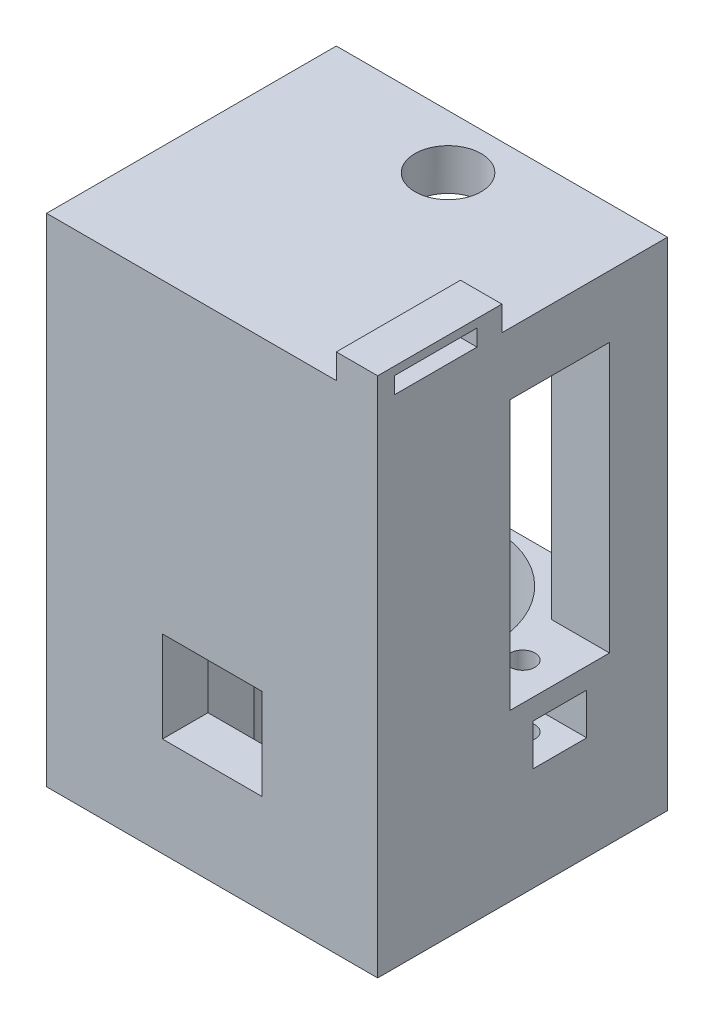
SolidWorks part; units mm, degrees
ref_plane "Plano frontal" through (0, 0, 0) normal (0, 0, 1) x (1, 0, 0)
ref_plane "Plano superior" through (0, 0, 0) normal (0, 1, 0) x (1, 0, 0)
ref_plane "Plano direito" through (0, 0, 0) normal (1, 0, 0) x (0, 0, -1)
sketch "Esboço2" plane through (0, 0, 0) normal (0, 1, 0) x (1, 0, 0)
  line L1 (0, 0) -> (40, 0)
  line L2 (0, 0) -> (0, 35)
  line L3 (0, 35) -> (40, 35)
  line L4 (40, 0) -> (40, 35)
  dimension "D1" = 40
  dimension "D2" = 35
extrude "Base" add sketch "Esboço2" along normal blind 20
sketch "Esboço3" plane through (0, 20, 0) normal (0, 1, 0) x (1, 0, 0)
  line L0 (20, -2.1425) -> (20, 46.202) construction
  line L1 (-2.8555, 22) -> (47.4642, 22) construction
  line L2 (40, 0) -> (40, 35) construction
  line L3 (40, 35) -> (0, 35) construction
  line L5 (11.25, 5.5) -> (28.75, 5.5)
  line L6 (11.25, 5.5) -> (11.25, 14.5)
  line L7 (11.25, 14.5) -> (28.75, 14.5)
  line L8 (28.75, 5.5) -> (28.75, 14.5)
  line L9 (11.25, 5.5) -> (28.75, 14.5) construction
  line L10 (11.25, 14.5) -> (28.75, 5.5) construction
  circle A0 centre (20, 22) radius 12
  point P10 (20, 10)
  dimension "D1" = 24
  dimension "D2" = 20
  dimension "D3" = 13
  dimension "D4" = 17.5
  dimension "D5" = 9
  dimension "D6" = 16.5
extrude "Furo do encaixe do motor" cut sketch "Esboço3" against normal through all contours A0 L7 L6 L5 L8 | L7 A0 | L7 A0 region at (20, 20, -8.4409) region at (20, 20, -23.3816) region at (20, 20, -12.6552)
sketch "Esboço5" plane through (0, 20, 0) normal (0, 1, 0) x (1, 0, 0)
  line L0 (41.6655, 22) -> (-3.8205, 22) construction
  line L1 (20, 37.517) -> (20, 6.483) construction
  circle A0 centre (4.5, 22) radius 1.5
  circle A1 centre (35.5, 22) radius 1.5
  point P10 (20, 22)
  dimension "D1" = 3
  dimension "D2" = 3
  dimension "D3" = 15.5
  dimension "D4" = 15.5
extrude "Furo dos parafusos do motor" cut sketch "Esboço5" against normal through all
sketch "Esboço6" plane through (40, 0, 0) normal (1, 0, 0) x (0, 0, -1)
  line L0 (22, 21.0896) -> (22, -1.5414) construction
  line L1 (35, 20) -> (35, 0) construction
  line L2 (0, 20) -> (35, 20) construction
  line L3 (18.75, 17.5) -> (25.25, 17.5)
  line L4 (18.75, 17.5) -> (18.75, 12.5)
  line L5 (18.75, 12.5) -> (25.25, 12.5)
  line L6 (25.25, 17.5) -> (25.25, 12.5)
  line L7 (18.75, 17.5) -> (25.25, 12.5) construction
  line L8 (18.75, 12.5) -> (25.25, 17.5) construction
  point P4 (22, 15)
  dimension "D1" = 13
  dimension "D2" = 6.5
  dimension "D3" = 5
  dimension "D4" = 5
extrude "Furo da arruela para parafusos do motor" cut sketch "Esboço6" against normal through all
sketch "Esboço7" plane through (0, 20, 0) normal (0, 1, 0) x (1, 0, 0)
  line L0 (20, 16.9507) -> (20, -1.8604) construction
  line L1 (40, 0) -> (40, 35) construction
  line L3 (14, -3.2615) -> (26, -3.2615)
  line L4 (14, -3.2615) -> (14, 18.3519)
  line L5 (14, 18.3519) -> (26, 18.3519)
  line L6 (26, -3.2615) -> (26, 18.3519)
  line L7 (14, -3.2615) -> (26, 18.3519) construction
  line L8 (14, 18.3519) -> (26, -3.2615) construction
  point P4 (20, 7.5452)
  dimension "D1" = 20
  dimension "D2" = 12
extrude "Calha para os cabos do motor" cut sketch "Esboço7" against normal blind 8
sketch "Esboço10" plane through (0, 20, 0) normal (0, 1, 0) x (1, 0, 0)
  line L0 (40, 0) -> (40, 35) construction
  line L1 (0, 35) -> (7, 35)
  line L2 (0, 35) -> (0, 28)
  line L3 (0, 28) -> (7, 28)
  line L4 (7, 35) -> (7, 28)
  line L5 (40, 35) -> (33, 35)
  line L6 (40, 35) -> (40, 28)
  line L7 (40, 28) -> (33, 28)
  line L8 (33, 35) -> (33, 28)
  line L9 (0, 0) -> (40, 0)
  line L10 (0, 0) -> (0, 5.5)
  line L11 (0, 5.5) -> (40, 5.5)
  line L12 (40, 0) -> (40, 5.5)
  line L14 (0, 5.5) -> (7, 5.5)
  line L15 (0, 5.5) -> (0, 16)
  line L16 (0, 16) -> (7, 16)
  line L17 (7, 5.5) -> (7, 16)
  line L18 (40, 5.5) -> (33, 5.5)
  line L19 (40, 5.5) -> (40, 16)
  line L20 (40, 16) -> (33, 16)
  line L21 (33, 5.5) -> (33, 16)
  line M13 (28.75, 5.5) -> (26, 5.5)
  line M14 (26, 5.5) -> (26, 0)
  line M15 (26, 0) -> (40, 0)
  line M16 (40, 0) -> (40, 35)
  line M17 (40, 35) -> (0, 35)
  line M18 (0, 35) -> (0, 0)
  line M19 (0, 0) -> (14, 0)
  line M20 (14, 0) -> (14, 5.5)
  line M21 (14, 5.5) -> (11.25, 5.5)
  dimension "D1" = 5.5
  dimension "D2" = 7
  dimension "D3" = 7
  dimension "D4" = 7
  dimension "D5" = 7
  dimension "D6" = 7
  dimension "D7" = 7
  dimension "D8" = 10.5
  dimension "D9" = 10.5
extrude "Base extendida" add sketch "Esboço10" along normal blind 35 contours L11 L17 L16 M18 | L11 M18 M19 M20 M21 | L11 M13 M14 M15 M16 | L11 L9 M20 M14 | L21 L11 L20 M16 | L8 L7 M17 M16 | L4 L3 M17 M18 region at (3.5, 20, -31.5) region at (36.5, 20, -31.5) region at (3.5, 20, -10.75) region at (7, 20, -2.75) region at (36.5, 20, -10.75) region at (20, 20, -2.75) region at (33, 20, -2.75)
sketch "Esboço11" plane through (7, 0, 0) normal (1, 0, 0) x (0, 0, -1)
  line L0 (16, 55) -> (16, 45)
  line L1 (16, 55) -> (16, 20) construction
  line L2 (16, 55) -> (5.5, 55)
  line L3 (5.5, 55) -> (16, 55) construction
  line L4 (5.5, 55) -> (5.5, 30.0044)
  line L5 (16, 45) -> (5.5, 30.0044)
  point P9 (10.75, 55)
  point P10 (5.5, 25.209)
  dimension "D1" = 10.5
  dimension "D2" = 35
  dimension "D3" = 10
extrude "Chanfro da base extendida" add sketch "Esboço11" along normal through all
sketch "Esboço12" plane through (0, 0, -16) normal (0, 0, -1) x (-1, 0, 0)
  line L1 (-40, 55) -> (-33, 55)
  line L2 (-40, 55) -> (-40, 52.5)
  line L3 (-40, 52.5) -> (-33, 52.5)
  line L4 (-33, 55) -> (-33, 52.5)
  dimension "D1" = 2.5
  dimension "D2" = 7
extrude "Ponte 1" add sketch "Esboço12" along normal through all
sketch "Esboço13" plane through (0, 0, -16) normal (0, 0, -1) x (-1, 0, 0)
  line L1 (0, 55) -> (-7, 55)
  line L2 (0, 55) -> (0, 52.5)
  line L3 (0, 52.5) -> (-7, 52.5)
  line L4 (-7, 55) -> (-7, 52.5)
  dimension "D1" = 2.5
  dimension "D2" = 7
extrude "Ponte 2" add sketch "Esboço13" along normal through all
sketch "Esboço14" plane through (0, 55, 0) normal (0, 1, 0) x (1, 0, 0)
  line L1 (0, 0) -> (40, 0)
  line L2 (0, 0) -> (0, 35)
  line L3 (0, 35) -> (40, 35)
  line L4 (40, 0) -> (40, 35)
extrude "Telhado" add sketch "Esboço14" along normal blind 5
sketch "Esboço16" plane through (0, 60, 0) normal (0, 1, 0) x (1, 0, 0)
  line L1 (40, 0) -> (35, 0)
  line L2 (40, 0) -> (40, 15)
  line L3 (40, 15) -> (35, 15)
  line L4 (35, 0) -> (35, 15)
  dimension "D1" = 5
  dimension "D2" = 15
extrude "Ressalto-extrusão6" add sketch "Esboço16" along normal blind 3
sketch "Esboço17" plane through (40, 0, 0) normal (1, 0, 0) x (0, 0, -1)
  line L0 (15, 60) -> (35, 60) construction
  line L1 (2, 60) -> (12, 60)
  line L2 (2, 60) -> (2, 62)
  line L3 (2, 62) -> (12, 62)
  line L4 (12, 60) -> (12, 62)
  line L5 (0, 63) -> (0, 0) construction
  dimension "D1" = 2
  dimension "D2" = 0
  dimension "D3" = 10
  dimension "D4" = 2
extrude "Corte-extrusão6" cut sketch "Esboço17" against normal blind 8
sketch "Esboço18" plane through (0, 60, 0) normal (0, 1, 0) x (1, 0, 0)
  line L0 (20, 37.438) -> (20, -2.8891) construction
  line L1 (40, 15) -> (40, 35) construction
  line L2 (40, 35) -> (0, 35) construction
  circle A0 centre (20, 28.5) radius 4
  dimension "D2" = 8
  dimension "D3" = 6.5
  dimension "D1" = 20
extrude "Furo do Eixo" cut sketch "Esboço18" against normal blind 8
sketch "Esboço20" plane through (0, 0, -5.5) normal (0, 0, -1) x (-1, 0, 0)
  line L0 (-33, 20) -> (-7, 20) construction
  line L1 (-26, 17) -> (-14, 17)
  line L2 (-26, 17) -> (-26, 23)
  line L3 (-26, 23) -> (-14, 23)
  line L4 (-14, 17) -> (-14, 23)
  line L5 (-26, 17) -> (-14, 23) construction
  line L6 (-26, 23) -> (-14, 17) construction
  point P0 (-20, 20)
  dimension "D1" = 12
  dimension "D2" = 6
extrude "Corte-extrusão8" cut sketch "Esboço20" against normal blind 15
